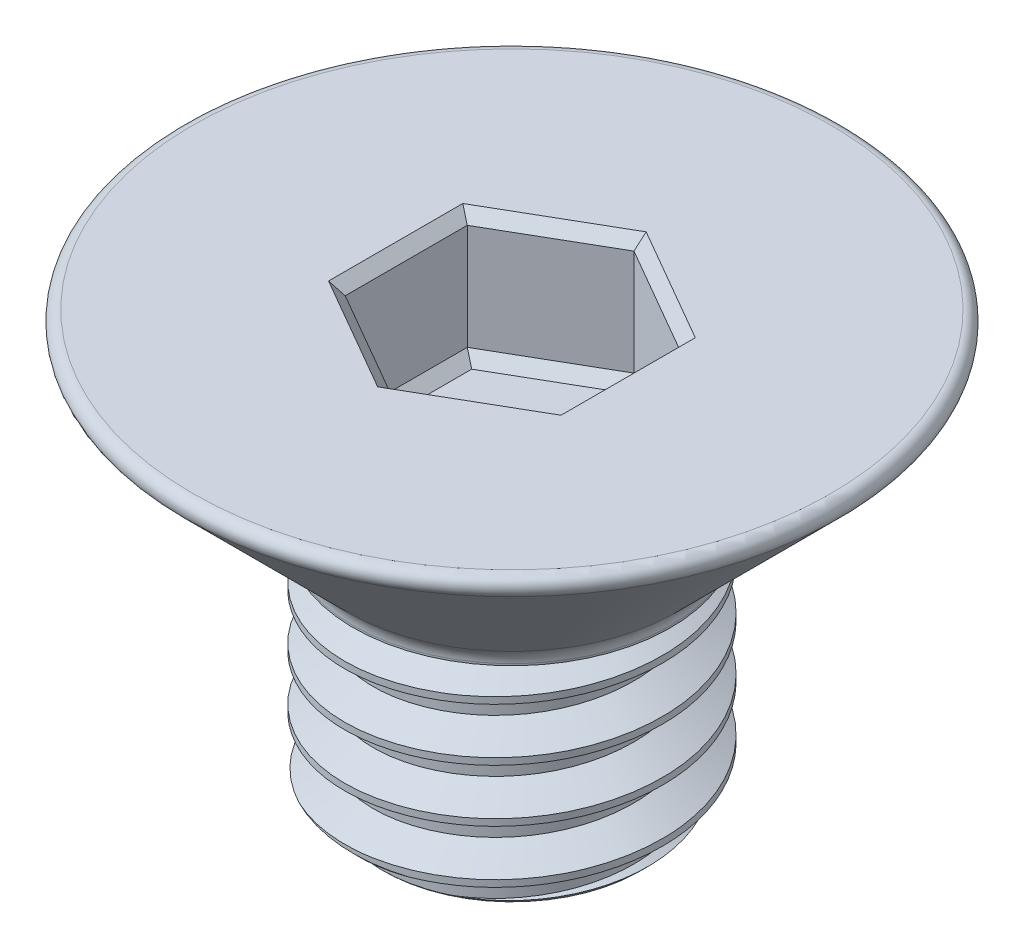
SolidWorks part; units mm, degrees
material "AISI Type A2 Tool Steel"
ref_plane "Front Plane" through (0, 0, 0) normal (0, 0, 1) x (1, 0, 0)
ref_plane "Top Plane" through (0, 0, 0) normal (0, 1, 0) x (1, 0, 0)
ref_plane "Right Plane" through (0, 0, 0) normal (1, 0, 0) x (0, 0, -1)
sketch "Sketch1" plane through (0, 0, 0) normal (0, 1, 0) x (1, 0, 0)
  circle A0 centre (0, 0) radius 1.5
  dimension "D1" = 3
extrude "Boss-Extrude1" add sketch "Sketch1" along normal blind 2.14
thread "Thread1" pitch 0.5 method cut profile "Thread Profile1" start angle 0, offset 1, length 0, pitch 0.5, diameter 3
ref_plane "Plane1" through (-1.5, 3.14, 0) normal (0, 0, 1) x (-1, 0, 0)
sketch "Thread Profile1" plane through (-1.5, 3.14, 0) normal (0, 0, 1) x (-1, 0, 0)
  line L0 (0, 0) -> (0, 0.5) construction
  line L11 (0, 0) -> (0, 0.4375)
  line L12 (0, 0.4375) -> (-0.2706, 0.2812)
  line L13 (-0.2706, 0.2812) -> (-0.2706, 0.1562)
  line L15 (-0.2706, 0.1562) -> (0, 0)
  line L17 (-0.2706, 0.2187) -> (0, 0.2187) construction
  point P2 (0, 0)
  dimension "Pitch" = 0.5
  dimension "Profile_Angle" = 60
  dimension "Profile_Land" = 0.125
  dimension "Profile_Height" = 0.2706
sketch "Sketch5" plane through (0, 2.14, 0) normal (0, 1, 0) x (1, 0, 0)
  circle A0 centre (0, 0) radius 1.5
  dimension "D1" = 3
extrude "Boss-Extrude2" add sketch "Sketch5" along normal blind 0.1
sketch "Sketch6" plane through (0, 2.24, 0) normal (0, 1, 0) x (1, 0, 0)
  circle A0 centre (0, 0) radius 1.5
  dimension "D1" = 3
extrude "Boss-Extrude3" add sketch "Sketch6" along normal blind 1.76 draft 45 draft outward yes
sketch "Sketch7" plane through (0, 0, 0) normal (0, 0, 1) x (1, 0, 0)
  line L0 (0, 0) -> (0, 0.1997) construction
  line L1 (0, 0) -> (1.51, 0) construction
  line L2 (1.51, 0) -> (1.51, 0.3)
  line L3 (1.51, 0.3) -> (1.21, 0)
  line L4 (1.21, 0) -> (1.51, 0)
  dimension "D1" = 45
  dimension "D2" = 0.3
  dimension "D3" = 1.51
revolve "Cut-Revolve1" cut sketch "Sketch7" angle 360 about L0
fillet "Fillet1" radius 0.1 1 edges at (0, 4, 3.26)
fillet "Fillet2" radius 0.2 1 edges at (0, 2.24, 1.5)
sketch "Sketch8" plane through (0, 4, 0) normal (0, 1, 0) x (1, 0, 0)
  line L1 (0, 1.1547) -> (-1, 0.5774)
  line L2 (-1, 0.5774) -> (-1, -0.5774)
  line L3 (-1, -0.5774) -> (0, -1.1547)
  line L4 (0, -1.1547) -> (1, -0.5774)
  line L5 (1, -0.5774) -> (1, 0.5774)
  line L6 (1, 0.5774) -> (0, 1.1547)
  circle A0 centre (0, 0) radius 1 construction
  dimension "D1" = 2
extrude "Cut-Extrude1" cut sketch "Sketch8" against normal blind 1.1
chamfer "Chamfer1" distance 0.1 angle 45 6 edges at (-1, 4, 0) (-0.5, 4, 0.866) (0.5, 4, 0.866) (1, 4, 0) (0.5, 4, -0.866) (-0.5, 4, -0.866)
sketch "Sketch9" plane through (0, 2.9, 0) normal (0, 1, 0) x (1, 0, 0)
  line L1 (0, 1.1547) -> (-1, 0.5774)
  line L2 (-1, 0.5774) -> (-1, -0.5774)
  line L3 (-1, -0.5774) -> (0, -1.1547)
  line L4 (0, -1.1547) -> (1, -0.5774)
  line L5 (1, -0.5774) -> (1, 0.5774)
  line L6 (1, 0.5774) -> (0, 1.1547)
  circle A0 centre (0, 0) radius 1 construction
extrude "Cut-Extrude2" cut sketch "Sketch9" against normal blind 0.1 draft 45
